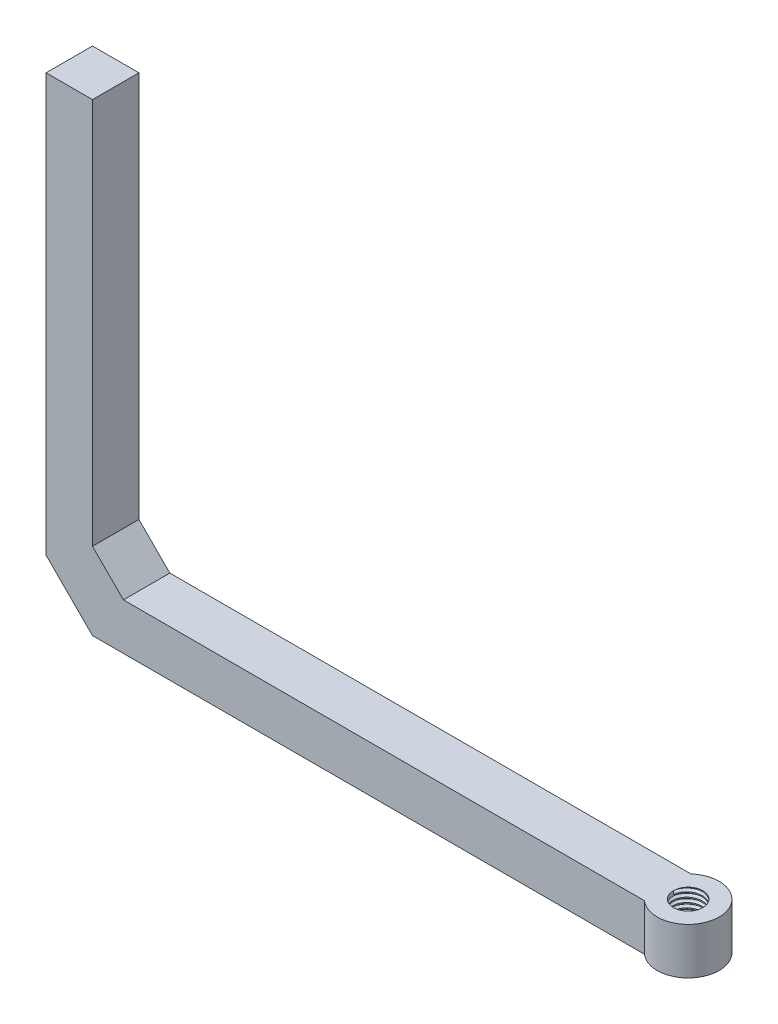
SolidWorks part; units mm, degrees
material "Plain Carbon Steel"
ref_plane "Front Plane" through (0, 0, 0) normal (0, 0, 1) x (1, 0, 0)
ref_plane "Top Plane" through (0, 0, 0) normal (0, 1, 0) x (1, 0, 0)
ref_plane "Right Plane" through (0, 0, 0) normal (1, 0, 0) x (0, 0, -1)
sketch "Sketch1" plane through (0, 0, 0) normal (0, 0, 1) x (1, 0, 0)
  line L0 (0, 0) -> (0, 15)
  line L1 (0, 15) -> (-175, 15)
  line L2 (-185, 25) -> (-185, 150)
  line L3 (-185, 150) -> (-200, 150)
  line L4 (-200, 150) -> (-200, 15)
  line L5 (-185, 0) -> (0, 0)
  line L6 (-200, 15) -> (-185, 0)
  line L7 (-175, 15) -> (-185, 25)
  point P4 (-185, 15)
  point P6 (-200, 0)
  point P7 (0, 0)
  dimension "D1" = 15
  dimension "D2" = 15
  dimension "D3" = 200
  dimension "D4" = 150
extrude "Boss-Extrude3" add sketch "Sketch1" along normal blind 15
sketch "Sketch5" plane through (0, 0, 0) normal (0, 1, 0) x (1, 0, 0)
  line L0 (0, -15) -> (0, 0) construction
  circle A0 centre (0, -7.5) radius 10
  dimension "D1" = 20
extrude "Boss-Extrude4" add sketch "Sketch5" along normal blind 15
sketch "Sketch6" plane through (0, 15, 0) normal (0, 1, 0) x (1, 0, 0)
  circle A0 centre (0, -7.5) radius 4.75
  arc A1 (-6.6144, -15) -> (-6.6144, 0) centre (0, -7.5) ccw construction
  dimension "D1" = 9.5
extrude "Cut-Extrude1" cut sketch "Sketch6" against normal blind 15
thread "Thread1" pitch 1.5 method cut profile "Thread Profile2" start angle 0, offset 0, length 0, pitch 1.5, diameter 9.5
ref_plane "Plane2" through (-4.75, 15, 7.5) normal (0, 0, 1) x (-1, 0, 0)
sketch "Thread Profile2" plane through (-4.75, 15, 7.5) normal (0, 0, 1) x (-1, 0, 0)
  line L0 (0, 0) -> (0, 1.5) construction
  line L1 (0, 0) -> (0.8119, 0.4687)
  line L2 (0.8119, 0.4687) -> (0.8119, 0.6562)
  line L3 (0.8119, 0.6562) -> (0, 1.125)
  line L4 (0.8119, 0.5625) -> (0, 0.5625) construction
  line L11 (0, 0) -> (0, 1.125)
  point P2 (0, 0)
  dimension "Pitch" = 1.5
  dimension "Profile_Angle" = 60
  dimension "Profile_Land" = 0.1875
  dimension "Profile_Height" = 0.8119
